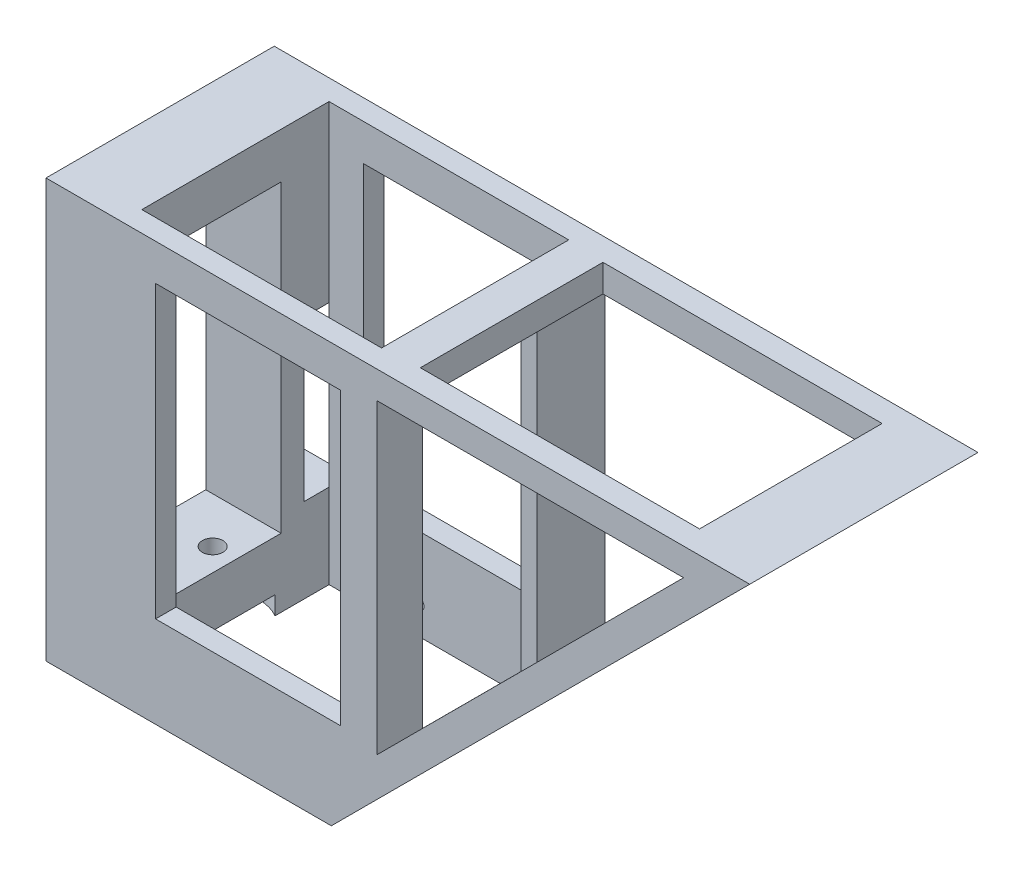
SolidWorks part; units mm, degrees
ref_plane "Plan de face" through (0, 0, 0) normal (0, 0, 1) x (1, 0, 0)
ref_plane "Plan de dessus" through (0, 0, 0) normal (0, 1, 0) x (1, 0, 0)
ref_plane "Plan de droite" through (0, 0, 0) normal (1, 0, 0) x (0, 0, -1)
sketch "Main-Sketch" plane through (0, 0, 0) normal (0, 0, 1) x (1, 0, 0)
  line L0 (0, 91.65) -> (154.15, 91.65)
  line L1 (154.15, 91.65) -> (62.5, 0)
  line L2 (62.5, 0) -> (0, 0)
  line L3 (0, 0) -> (0, 91.65)
  dimension "D1" = 62.5
  dimension "D2" = 154.15
  dimension "D3" = 135
extrude "Main-Extrusion" add sketch "Main-Sketch" along normal blind 50
ref_plane "Plan1" through (0, 0, 45) normal (0, 0, 1) x (1, 0, 0)
sketch "Fix-Bottom-Sheet-Sketch" plane through (0, 0, 0) normal (0, 0, -1) x (-1, 0, 0)
  line L0 (-62.5, 0) -> (-154.15, 91.65) construction
  circle A0 centre (-105.4994, 50.0705) radius 1.35
  circle A1 centre (-35.9453, 6.2286) radius 1.35
  dimension "D1" = 2.7
  dimension "D2" = 5
  dimension "D3" = 66
extrude "Fix-Bottom-Sheet-Extrusion" cut sketch "Fix-Bottom-Sheet-Sketch" against normal blind 10
sketch "Esquisse2" plane through (0, 0, 0) normal (0, -1, 0) x (-1, 0, 0)
  line L0 (0, -50) -> (0, 0) construction
  line L1 (-16.5, -45.5) -> (-69, -45.5)
  line L2 (-16.5, -45.5) -> (-16.5, -4.5)
  line L3 (-16.5, -4.5) -> (-69, -4.5)
  line L4 (-69, -45.5) -> (-69, -4.5)
  line L5 (0, -50) -> (-62.5, -50) construction
  point P4 (-16.5, -25)
  point P7 (0, -25)
  point P8 (0, 0)
  point P11 (-31.25, -50)
  point P12 (-69, -25)
  point P13 (-16.3275, -4.5)
  dimension "D1" = 41
  dimension "D2" = 16.5
  dimension "D3" = 52.5
extrude "Enlèv. mat.-Extru.2" cut sketch "Esquisse2" against normal through all
sketch "Esquisse3" plane through (0, 0, 50) normal (0, 0, 1) x (1, 0, 0)
  line L0 (72.5, 85.65) -> (72.5, 18.4853)
  line L1 (72.5, 18.4853) -> (139.6647, 85.65)
  line L2 (139.6647, 85.65) -> (72.5, 85.65)
  line L3 (62.5, 0) -> (154.15, 91.65) construction
  line L4 (154.15, 91.65) -> (0, 91.65) construction
  point P7 (76.6426, 83.65)
  dimension "D1" = 6
  dimension "D2" = 6
  dimension "D3" = 10
extrude "Enlèv. mat.-Extru.3" cut sketch "Esquisse3" against normal through all
sketch "Esquisse4" plane through (0, 0, 0) normal (0, 0, -1) x (-1, 0, 0)
  line L0 (0, 91.65) -> (0, 0) construction
  line L1 (0, 18.5) -> (-16.5, 18.5)
  line L2 (0, 18.5) -> (0, 53.5)
  line L3 (0, 53.5) -> (-16.5, 53.5)
  line L4 (-16.5, 18.5) -> (-16.5, 53.5)
  line L5 (0, 0) -> (-62.5, 0) construction
  dimension "D1" = 16.5
  dimension "D2" = 18.5
  dimension "D3" = 35
extrude "Enlèv. mat.-Extru.4" cut sketch "Esquisse4" against normal blind 10
sketch "Esquisse6" plane through (0, 0, 0) normal (0, -1, 0) x (1, 0, 0)
  line L0 (16.5, 45.5) -> (16.5, 4.5) construction
  line L1 (0, 50) -> (0, 0) construction
  circle A0 centre (11.5, 25) radius 10
  point P7 (0, 25)
  dimension "D1" = 20
  dimension "D2" = 5
extrude "Enlèv. mat.-Extru.6" cut sketch "Esquisse6" against normal blind 4
sketch "Esquisse7" plane through (0, 4, 0) normal (0, -1, 0) x (1, 0, 0)
  circle A0 centre (11.5, 25) radius 2.25
  circle A1 centre (11.5, 25) radius 10 construction
  dimension "D1" = 4.5
extrude "Enlèv. mat.-Extru.7" cut sketch "Esquisse7" against normal blind 15
ref_plane "Plan2" through (0, 15, 0) normal (0, -1, 0) x (1, 0, 0)
ref_plane "Plan3" through (0, 85.65, 0) normal (0, 1, 0) x (1, 0, 0)
sketch "Esquisse8" plane through (0, 85.65, 0) normal (0, 1, 0) x (-1, 0, 0)
  line L1 (-11.5, 40) -> (-5, 40)
  line L2 (-11.5, 40) -> (-11.5, 15)
  line L3 (-11.5, 15) -> (-5, 15)
  line L4 (-5, 40) -> (-5, 15)
  line L6 (-16.5, 45.5) -> (-16.5, 4.5) construction
  line L7 (0, 50) -> (0, 0) construction
  line L8 (-154.15, 0) -> (0, 0) construction
  line L9 (-154.15, 50) -> (0, 50) construction
  dimension "D1" = 5
  dimension "D2" = 5
  dimension "D3" = 15
  dimension "D4" = 10
extrude "Enlèv. mat.-Extru.8" cut sketch "Esquisse8" against normal up to surface (70.65 mm away) up to plane "Plan2"
sketch "Esquisse9" plane through (0, 0, 0) normal (-1, 0, 0) x (0, 0, 1)
  line L0 (-27.5, 15) -> (27.5, 15) construction
  line L1 (40, 81.65) -> (15, 81.65)
  line L2 (40, 81.65) -> (40, 15)
  line L3 (40, 15) -> (15, 15)
  line L4 (15, 81.65) -> (15, 15)
  line L5 (50, 91.65) -> (0, 91.65) construction
  line L6 (50, 91.65) -> (50, 0) construction
  line L7 (0, 91.65) -> (0, 53.5) construction
  point P4 (27.5, 15)
  dimension "D1" = 10
  dimension "D2" = 10
  dimension "D3" = 15
extrude "Enlèv. mat.-Extru.9" cut sketch "Esquisse9" against normal up to surface (72.5 mm away) up to face at (72.5, 52.0676, 25)
sketch "Esquisse10" plane through (0, 91.65, 0) normal (0, 1, 0) x (1, 0, 0)
  line L0 (154.15, -50) -> (0, -50) construction
  line L1 (138.15, -45) -> (77, -45)
  line L2 (138.15, -45) -> (138.15, -5)
  line L3 (138.15, -5) -> (77, -5)
  line L4 (77, -45) -> (77, -5)
  line L5 (154.15, 0) -> (0, 0) construction
  line L6 (69, -4.5) -> (69, -45.5) construction
  line L7 (154.15, -50) -> (154.15, 0) construction
  dimension "D1" = 5
  dimension "D2" = 5
  dimension "D3" = 8
  dimension "D4" = 16
extrude "Enlèv. mat.-Extru.10" cut sketch "Esquisse10" against normal up to next
sketch "Esquisse11" plane through (27.0074, -27.0074, 0) normal (-0.7071, 0.7071, 0) x (0.7071, 0.7071, 0)
  line L0 (173.8068, -50) -> (173.8068, 0) construction
  line L1 (153.8068, -45) -> (69.3363, -45)
  line L2 (153.8068, -45) -> (153.8068, -5)
  line L3 (153.8068, -5) -> (69.3363, -5)
  line L4 (69.3363, -45) -> (69.3363, -5)
  line L5 (64.3363, -50) -> (159.3216, -50) construction
  line L6 (110.9114, 0) -> (159.3216, 0) construction
  line L7 (64.3363, 0) -> (64.3363, -15) construction
  dimension "D1" = 20
  dimension "D2" = 5
  dimension "D3" = 5
  dimension "D4" = 5
extrude "Enlèv. mat.-Extru.11" cut sketch "Esquisse11" against normal blind 2
sketch "Esquisse12" plane through (0, 0, 0) normal (0, 0, -1) x (-1, 0, 0)
  line L0 (-154.15, 91.65) -> (0, 91.65) construction
  line L1 (-24, 83.65) -> (-64.5, 83.65)
  line L2 (-24, 83.65) -> (-24, 20)
  line L3 (-24, 20) -> (-64.5, 20)
  line L4 (-64.5, 20) -> (-64.5, 83.65)
  line L6 (0, 91.65) -> (0, 53.5) construction
  line L7 (0, 0) -> (-62.5, 0) construction
  line L9 (-72.5, 85.65) -> (-72.5, 18.4853) construction
  dimension "D1" = 8
  dimension "D3" = 24
  dimension "D4" = 20
  dimension "D5" = 8
extrude "Enlèv. mat.-Extru.12" cut sketch "Esquisse12" against normal through all
